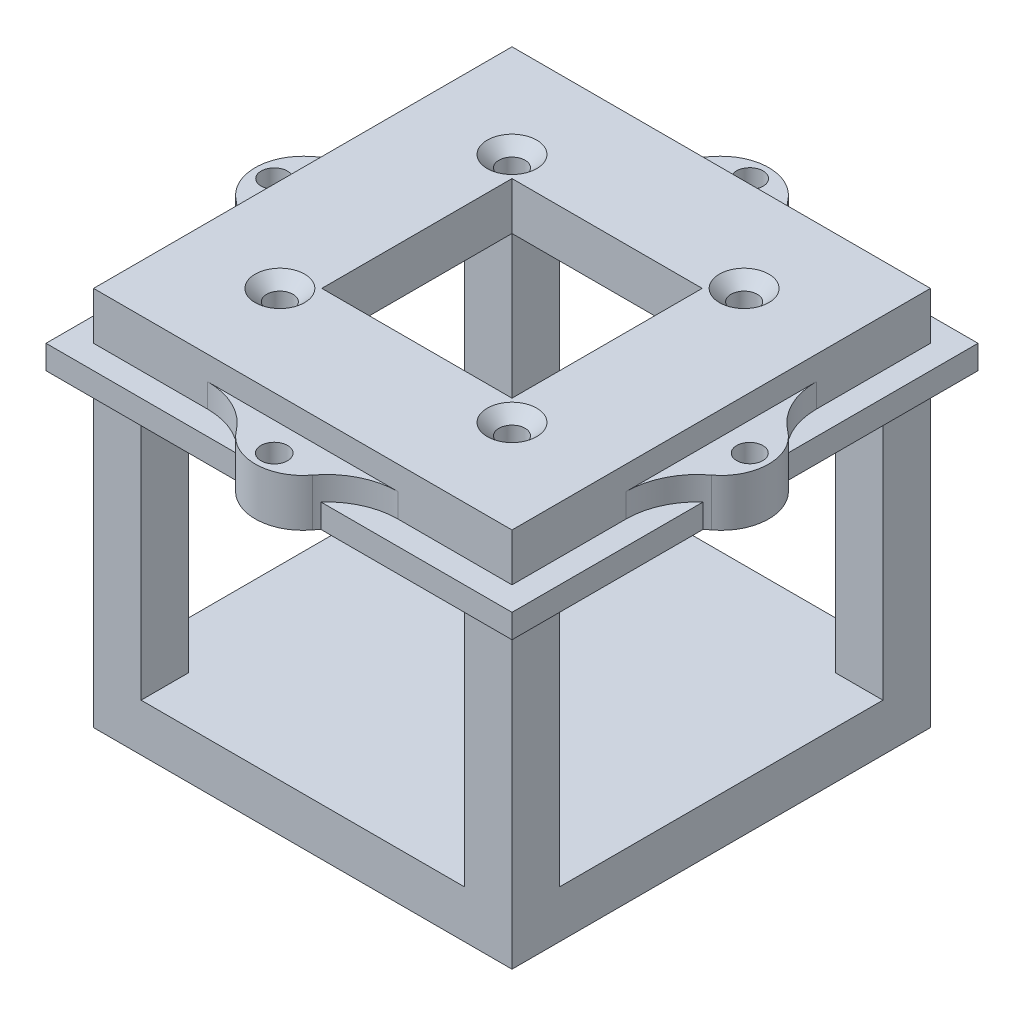
SolidWorks part; units mm, degrees
ref_plane "Front Plane" through (0, 0, 0) normal (0, 0, 1) x (1, 0, 0)
ref_plane "Top Plane" through (0, 0, 0) normal (0, 1, 0) x (1, 0, 0)
ref_plane "Right Plane" through (0, 0, 0) normal (1, 0, 0) x (0, 0, -1)
sketch "Sketch1" plane through (0, 0, 0) normal (0, 1, 0) x (1, 0, 0)
  line L1 (0, 0) -> (55.88, 0)
  line L2 (0, 0) -> (0, 55.88)
  line L3 (0, 55.88) -> (55.88, 55.88)
  line L4 (55.88, 0) -> (55.88, 55.88)
  dimension "D1" = 55.88
  dimension "D2" = 55.88
extrude "Boss-Extrude1" add sketch "Sketch1" along normal blind 50.8
sketch "Sketch2" plane through (0, 0, 0) normal (0, 0, 1) x (1, 0, 0)
  line L0 (0, 50.8) -> (55.88, 50.8) construction
  line L1 (6.35, 6.35) -> (49.53, 6.35)
  line L2 (6.35, 6.35) -> (6.35, 44.45)
  line L3 (6.35, 44.45) -> (49.53, 44.45)
  line L4 (49.53, 6.35) -> (49.53, 44.45)
  line L5 (0, 50.8) -> (0, 0) construction
  line L6 (0, 0) -> (55.88, 0) construction
  line L7 (0, 50.8) -> (0, 0) construction
  point P4 (27.94, 44.45)
  point P7 (27.94, 50.8)
  point P8 (6.35, 25.4)
  point P11 (0, 25.4)
  dimension "D1" = 6.35
  dimension "D2" = 6.35
extrude "Cut-Extrude1" cut sketch "Sketch2" against normal through all
sketch "Sketch3" plane through (55.88, 0, 0) normal (1, 0, 0) x (0, 0, -1)
  line L0 (0, 50.8) -> (55.88, 50.8) construction
  line L1 (6.35, 6.35) -> (49.53, 6.35)
  line L2 (6.35, 6.35) -> (6.35, 44.45)
  line L3 (6.35, 44.45) -> (49.53, 44.45)
  line L4 (49.53, 6.35) -> (49.53, 44.45)
  line L5 (0, 50.8) -> (0, 0) construction
  point P4 (27.94, 44.45)
  point P7 (27.94, 50.8)
  point P8 (6.35, 25.4)
  point P11 (0, 25.4)
  dimension "D1" = 6.35
  dimension "D2" = 6.35
extrude "Cut-Extrude2" cut sketch "Sketch3" against normal through all
sketch "Sketch4" plane through (0, 50.8, 0) normal (0, 1, 0) x (1, 0, 0)
  line L0 (55.88, 0) -> (55.88, 55.88) construction
  line L6 (12.44, 49.09) -> (43.44, 49.09) construction
  line L7 (43.44, 49.09) -> (49.09, 43.44) construction
  line L8 (49.09, 43.44) -> (49.09, 12.44) construction
  line L9 (49.09, 12.44) -> (43.44, 6.79) construction
  line L10 (43.44, 6.79) -> (12.44, 6.79) construction
  line L11 (12.44, 6.79) -> (6.79, 12.44) construction
  line L12 (6.79, 12.44) -> (6.79, 43.44) construction
  line L13 (6.79, 43.44) -> (12.44, 49.09) construction
  line L14 (55.88, 55.88) -> (0, 55.88) construction
  line L15 (46.265, 9.615) -> (9.615, 46.265) construction
  line L16 (15.24, 40.64) -> (40.64, 40.64)
  line L17 (15.24, 40.64) -> (15.24, 15.24)
  line L18 (15.24, 15.24) -> (40.64, 15.24)
  line L19 (40.64, 40.64) -> (40.64, 15.24)
  line L20 (46.265, 46.265) -> (9.615, 9.615) construction
  circle A0 centre (43.44, 43.44) radius 1.75
  circle A1 centre (43.44, 12.44) radius 1.75
  circle A2 centre (12.44, 12.44) radius 1.75
  circle A3 centre (12.44, 43.44) radius 1.75
  point P7 (55.88, 27.94)
  point P16 (49.09, 27.94)
  point P17 (27.94, 49.09)
  point P20 (27.94, 55.88)
  dimension "D3" = 3.5
  dimension "D1" = 42.3
  dimension "D2" = 31
  dimension "D4" = 25.4
extrude "Cut-Extrude3" cut sketch "Sketch4" against normal up to surface (44.45 mm away) up to face at (27.94, 6.35, -27.94)
ref_axis "Axis1" through (12.44, 44.45, -12.44) along (0, 1, 0)
ref_axis "Axis2" through (12.44, 44.45, -43.44) along (0, 1, 0)
ref_axis "Axis3" through (43.44, 44.45, -43.44) along (0, 1, 0)
ref_axis "Axis4" through (43.44, 44.45, -12.44) along (0, 1, 0)
ref_plane "Plane1" through (43.44, 0, 0) normal (1, 0, 0) x (0, 0, -1)
ref_plane "Plane2" through (12.44, 0, 0) normal (1, 0, 0) x (0, 0, -1)
sketch "Sketch5" plane through (12.44, 0, 0) normal (1, 0, 0) x (0, 0, -1)
  line L0 (43.44, 50.8) -> (40.138, 50.8)
  line L1 (40.138, 50.8) -> (43.44, 47.498)
  line L2 (43.44, 47.498) -> (43.44, 50.8)
  line L3 (43.44, 44.45) -> (43.44, 50.8) construction
  line L4 (45.19, 50.8) -> (41.69, 50.8) construction
  dimension "D1" = 3.302
  dimension "D2" = 3.302
revolve "Cut-Revolve1" cut sketch "Sketch5" angle 360 about L2
sketch "Sketch6" plane through (12.44, 0, 0) normal (1, 0, 0) x (0, 0, -1)
  line L0 (12.44, 50.8) -> (9.138, 50.8)
  line L1 (9.138, 50.8) -> (12.44, 47.498)
  line L2 (12.44, 47.498) -> (12.44, 50.8)
  line L3 (12.44, 44.45) -> (12.44, 50.8) construction
  line L4 (46.742, 50.8) -> (40.138, 50.8) construction
  dimension "D1" = 3.302
  dimension "D2" = 3.302
revolve "Cut-Revolve2" cut sketch "Sketch6" angle 360 about L2
sketch "Sketch7" plane through (43.44, 0, 0) normal (1, 0, 0) x (0, 0, -1)
  line L0 (43.44, 50.8) -> (40.138, 50.8)
  line L1 (40.138, 50.8) -> (43.44, 47.498)
  line L2 (43.44, 47.498) -> (43.44, 50.8)
  line L3 (43.44, 44.45) -> (43.44, 50.8) construction
  line L4 (15.742, 50.8) -> (9.138, 50.8) construction
  dimension "D1" = 3.302
  dimension "D2" = 3.302
revolve "Cut-Revolve3" cut sketch "Sketch7" angle 360 about L2
sketch "Sketch8" plane through (43.44, 0, 0) normal (1, 0, 0) x (0, 0, -1)
  line L0 (12.44, 50.8) -> (9.138, 50.8)
  line L1 (9.138, 50.8) -> (12.44, 47.498)
  line L2 (12.44, 47.498) -> (12.44, 50.8)
  line L3 (12.44, 44.45) -> (12.44, 50.8) construction
  line L4 (46.742, 50.8) -> (40.138, 50.8) construction
  dimension "D1" = 3.302
  dimension "D2" = 3.302
revolve "Cut-Revolve4" cut sketch "Sketch8" angle 360 about L2
sketch "Sketch9" plane through (0, 44.45, 0) normal (0, -1, 0) x (1, 0, 0)
  line L0 (0, -49.53) -> (0, -6.35) construction
  line L1 (0, -40.64) -> (0, -15.24)
  line L2 (27.94, 0) -> (27.94, -55.88) construction
  line L3 (49.53, 0) -> (6.35, 0) construction
  line L4 (49.53, -55.88) -> (6.35, -55.88) construction
  line L5 (55.88, -40.64) -> (55.88, -15.24)
  line L6 (0, -27.94) -> (55.88, -27.94) construction
  line L7 (15.24, 0) -> (40.64, 0)
  line L8 (15.24, -55.88) -> (40.64, -55.88)
  arc A0 (0, -15.24) -> (-3.81, -22.86) centre (-9.525, -15.24) cw
  arc A1 (-3.81, -22.86) -> (-3.81, -33.02) centre (0, -27.94) ccw
  arc A2 (-3.81, -33.02) -> (0, -40.64) centre (-9.525, -40.64) cw
  arc A3 (59.69, -33.02) -> (55.88, -40.64) centre (65.405, -40.64) ccw
  arc A4 (59.69, -22.86) -> (59.69, -33.02) centre (55.88, -27.94) cw
  arc A5 (55.88, -15.24) -> (59.69, -22.86) centre (65.405, -15.24) ccw
  arc A6 (15.24, 0) -> (22.86, 3.81) centre (15.24, 9.525) ccw
  arc A7 (22.86, 3.81) -> (33.02, 3.81) centre (27.94, 0) cw
  arc A8 (33.02, 3.81) -> (40.64, 0) centre (40.64, 9.525) ccw
  arc A9 (15.24, -55.88) -> (22.86, -59.69) centre (15.24, -65.405) cw
  arc A10 (22.86, -59.69) -> (33.02, -59.69) centre (27.94, -55.88) ccw
  arc A11 (33.02, -59.69) -> (40.64, -55.88) centre (40.64, -65.405) cw
  point P11 (-6.35, -27.94)
  point P30 (27.94, 6.35)
  dimension "D4" = 6.35
  dimension "D1" = 6.35
  dimension "D2" = 25.4
  dimension "D3" = 25.4
extrude "Boss-Extrude2" add sketch "Sketch9" along normal blind 3.175 and the other way blind 3.175
sketch "Sketch10" plane through (0, 0, 0) normal (0, 0, 1) x (1, 0, 0)
  line L1 (49.53, 44.45) -> (59.055, 44.45)
  line L2 (49.53, 44.45) -> (49.53, 41.275)
  line L3 (49.53, 41.275) -> (59.055, 41.275)
  line L4 (59.055, 44.45) -> (59.055, 41.275)
  line L5 (49.53, 44.45) -> (40.64, 44.45) construction
  line L6 (27.94, 50.8) -> (27.94, 0) construction
  line L7 (0, 50.8) -> (55.88, 50.8) construction
  line L8 (0, 0) -> (55.88, 0) construction
  line L9 (6.35, 41.275) -> (-3.175, 41.275)
  line L10 (-3.175, 44.45) -> (-3.175, 41.275)
  line L11 (6.35, 44.45) -> (-3.175, 44.45)
  line L12 (6.35, 44.45) -> (6.35, 41.275)
  line L13 (49.53, 6.35) -> (49.53, 44.45) construction
  line L14 (55.88, 50.8) -> (55.88, 0) construction
  dimension "D1" = 3.175
extrude "Boss-Extrude5" add sketch "Sketch10" against normal up to surface (55.88 mm away) up to face at (27.94, 25.4, -55.88)
sketch "Sketch12" plane through (0, 0, -55.88) normal (0, 0, -1) x (-1, 0, 0)
  line L1 (-59.055, 41.275) -> (3.175, 41.275)
  line L2 (-59.055, 41.275) -> (-59.055, 44.45)
  line L3 (-59.055, 44.45) -> (3.175, 44.45)
  line L4 (3.175, 41.275) -> (3.175, 44.45)
extrude "Boss-Extrude6" add sketch "Sketch12" along normal blind 3.175 and the other way up to surface (6.35 mm away) other way up to face at (3.175, 23.8125, -49.53)
sketch "Sketch13" plane through (0, 0, 0) normal (0, 0, 1) x (1, 0, 0)
  line L1 (-3.175, 41.275) -> (59.055, 41.275)
  line L2 (-3.175, 41.275) -> (-3.175, 44.45)
  line L3 (-3.175, 44.45) -> (59.055, 44.45)
  line L4 (59.055, 41.275) -> (59.055, 44.45)
extrude "Boss-Extrude7" add sketch "Sketch13" along normal blind 3.175 and the other way up to surface (6.35 mm away) other way up to face at (52.705, 23.8125, -6.35)
sketch "Sketch11" plane through (0, 47.625, 0) normal (0, 1, 0) x (1, 0, 0)
  line L0 (-3.81, 33.02) -> (-3.81, 22.86) construction
  line L1 (59.69, 22.86) -> (59.69, 33.02) construction
  line L2 (22.86, -3.81) -> (33.02, -3.81) construction
  line L3 (22.86, 59.69) -> (33.02, 59.69) construction
  circle A0 centre (-3.81, 27.94) radius 1.75
  arc A1 (59.69, 22.86) -> (59.69, 33.02) centre (55.88, 27.94) ccw construction
  circle A2 centre (59.69, 27.94) radius 1.75
  circle A3 centre (27.94, -3.81) radius 1.778
  circle A4 centre (27.94, 59.69) radius 1.778
  dimension "D1" = 3.5
  dimension "D2" = 3.5
  dimension "D3" = 3.556
  dimension "D4" = 3.556
extrude "Cut-Extrude4" cut sketch "Sketch11" against normal through all
ref_plane "Plane3" through (0, 0, -27.94) normal (0, 0, -1) x (-1, 0, 0)
sketch "Sketch14" plane through (0, 0, -27.94) normal (0, 0, -1) x (-1, 0, 0)
  line L0 (-8.89, 0) -> (-24.765, -2.8885)
  line L1 (-27.94, -3.175) -> (-27.94, 0)
  line L2 (-27.94, 0) -> (-8.89, 0)
  line L3 (-55.88, 0) -> (0, 0) construction
  line L4 (-27.94, -3.175) -> (0.4871, -3.175) construction
  arc A0 (-24.765, -2.8885) -> (-27.94, -3.175) centre (-27.94, 14.5611) cw
  point P7 (-27.94, 0)
  dimension "D1" = 3.175
  dimension "D2" = 19.05
  dimension "D3" = 3.175
revolve "Revolve1" add sketch "Sketch14" angle 360 about L1
sketch "Sketch15" plane through (0, 41.275, 0) normal (0, -1, 0) x (1, 0, 0)
  circle A0 centre (-3.81, -27.94) radius 1.75
  circle A1 centre (-3.81, -27.94) radius 2.54
  arc A2 (-3.81, -22.86) -> (-3.81, -33.02) centre (0, -27.94) ccw construction
  circle A3 centre (-3.81, -27.94) radius 1.75 construction
  circle A4 centre (27.94, -59.69) radius 2.54
  circle A5 centre (27.94, -59.69) radius 1.778
  arc A6 (22.86, -59.69) -> (33.02, -59.69) centre (27.94, -55.88) ccw construction
  circle A7 centre (27.94, -59.69) radius 1.778 construction
extrude "Boss-Extrude8" add sketch "Sketch15" along normal blind 7.239
sketch "Sketch16" plane through (0, 34.036, 0) normal (0, -1, 0) x (1, 0, 0)
  line L0 (34.29, -59.69) -> (21.59, -59.69) construction
  line L1 (34.29, -62.23) -> (21.59, -62.23)
  line L2 (34.29, -57.15) -> (21.59, -57.15)
  line L4 (59.055, -59.055) -> (33.5405, -59.055) construction
  line L5 (-3.81, -34.29) -> (-3.81, -21.59) construction
  line L6 (-6.35, -34.29) -> (-6.35, -21.59)
  line L7 (-1.27, -34.29) -> (-1.27, -21.59)
  arc A0 (34.29, -62.23) -> (34.29, -57.15) centre (34.29, -59.69) ccw
  arc A1 (21.59, -57.15) -> (21.59, -62.23) centre (21.59, -59.69) ccw
  circle A2 centre (27.94, -59.69) radius 2.54 construction
  circle A3 centre (27.94, -59.69) radius 1.778 construction
  circle A4 centre (34.29, -59.69) radius 1.651
  circle A5 centre (21.59, -59.69) radius 1.651
  arc A6 (-6.35, -34.29) -> (-1.27, -34.29) centre (-3.81, -34.29) ccw
  arc A7 (-1.27, -21.59) -> (-6.35, -21.59) centre (-3.81, -21.59) ccw
  circle A8 centre (-3.81, -27.94) radius 1.75 construction
  circle A9 centre (-3.81, -27.94) radius 2.54 construction
  circle A10 centre (-3.81, -34.29) radius 1.651
  circle A11 centre (-3.81, -21.59) radius 1.651
  point P2 (27.94, -59.69)
  point P15 (-3.81, -27.94)
  dimension "D1" = 3.302
  dimension "D2" = 3.302
  dimension "D4" = 3.302
  dimension "D5" = 3.302
  dimension "D3" = 12.7
  dimension "D6" = 12.7
extrude "Boss-Extrude9" add sketch "Sketch16" along normal blind 3.175
